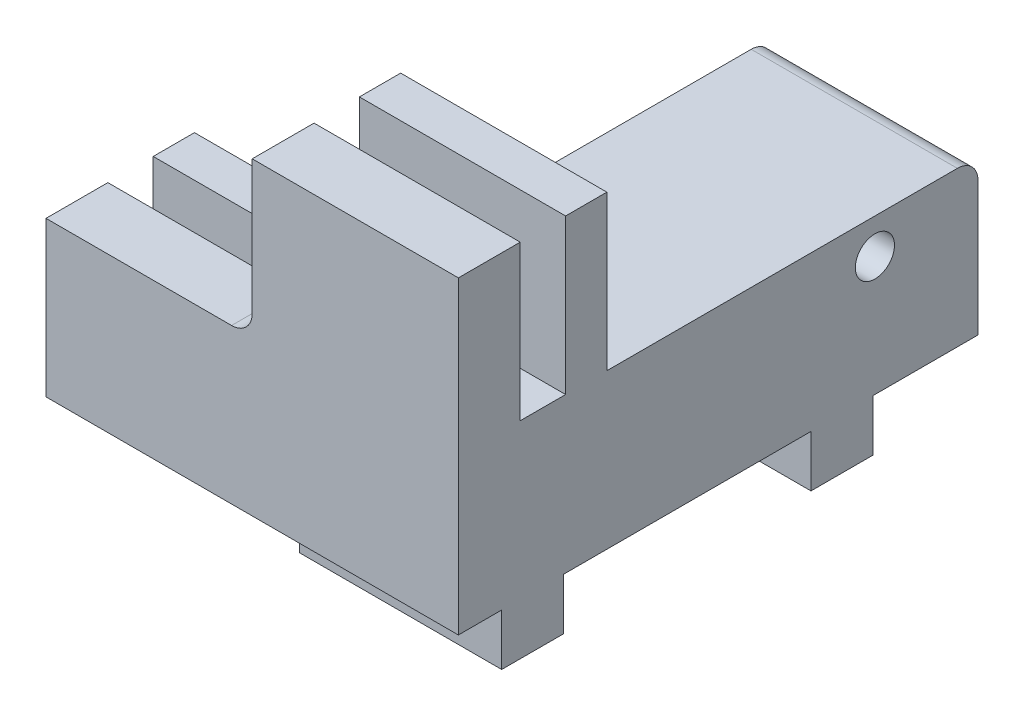
SolidWorks part; units mm, degrees
ref_plane "Front Plane" through (0, 0, 0) normal (0, 0, 1) x (1, 0, 0)
ref_plane "Top Plane" through (0, 0, 0) normal (0, 1, 0) x (1, 0, 0)
ref_plane "Right Plane" through (0, 0, 0) normal (1, 0, 0) x (0, 0, -1)
sketch "Sketch1" plane through (0, 0, 0) normal (1, 0, 0) x (0, 0, -1)
  line L0 (-33.4167, 0) -> (-33.4167, 19.05)
  line L1 (35.2044, 0) -> (-35.2044, 0) construction
  line L2 (-33.4167, 19.05) -> (-25.7967, 19.05)
  line L3 (-25.7967, 19.05) -> (-25.7967, 10.922)
  line L4 (-25.7967, 10.922) -> (-20.2087, 10.922)
  line L5 (-20.2087, 10.922) -> (-20.2087, 19.05)
  line L6 (-20.2087, 19.05) -> (30.5913, 19.05)
  line L7 (30.5913, 19.05) -> (30.5913, 0)
  line L8 (30.5913, 0) -> (-33.4167, 0)
  line L9 (-33.4167, 0) -> (30.5913, 0)
  line L10 (-20.2087, 10.922) -> (17.8913, 10.922)
  line L11 (17.8913, 10.922) -> (17.8913, 14.732)
  line L12 (-15.1287, 19.05) -> (-15.1287, 0)
  circle A0 centre (17.8913, 14.732) radius 2.413
  dimension "D1" = 4.826
  dimension "D2" = 5.588
  dimension "D3" = 8.128
  dimension "D4" = 38.1
  dimension "D5" = 3.81
  dimension "D6" = 50.8
  dimension "D7" = 19.05
  dimension "D8" = 7.62
  dimension "D9" = 5.08
extrude "Boss-Extrude1" add sketch "Sketch1" against normal blind 25.4 contours L12 L10 L4 L3 L2 L0 L9 | L12 L6 L5 L10 region at (0, 7.7154, 25.5352) region at (0, 14.986, 17.6687)
sketch "Sketch2" plane through (0, 0, 0) normal (1, 0, 0) x (0, 0, -1)
  line L0 (-33.4167, 19.05) -> (-33.4167, 38.1)
  line L1 (-33.4167, 38.1) -> (-25.7967, 38.1)
  line L2 (-25.7967, 38.1) -> (-25.7967, 19.05)
  line L3 (-33.4167, 19.05) -> (-33.4167, 0)
  line L4 (-33.4167, 0) -> (-15.1287, 0)
  line L5 (-15.1287, 0) -> (-15.1287, 19.05)
  line L6 (-15.1287, 19.05) -> (-15.1287, 38.1)
  line L7 (-15.1287, 38.1) -> (-20.2087, 38.1)
  line L8 (-20.2087, 38.1) -> (-20.2087, 19.05)
  line L9 (-20.2087, 19.05) -> (-20.2087, 10.922)
  line L10 (-20.2087, 10.922) -> (-25.7967, 10.922)
  line L11 (-25.7967, 10.922) -> (-25.7967, 19.05)
  line L12 (-15.1287, 0) -> (30.5913, 0)
  line L13 (30.5913, 0) -> (30.5913, 19.05)
  line L14 (30.5913, 19.05) -> (-15.1287, 19.05)
  circle A0 centre (17.8913, 14.732) radius 2.413
  line M3 (-15.1287, 0) -> (-15.1287, 19.05)
  line M4 (-15.1287, 19.05) -> (-20.2087, 19.05)
  line M5 (-20.2087, 19.05) -> (-20.2087, 10.922)
  line M6 (-20.2087, 10.922) -> (-25.7967, 10.922)
  line M7 (-25.7967, 10.922) -> (-25.7967, 19.05)
  line M8 (-25.7967, 19.05) -> (-33.4167, 19.05)
  line M9 (-33.4167, 19.05) -> (-33.4167, 0)
  line M10 (-33.4167, 0) -> (-15.1287, 0)
  dimension "D2" = 4.826
  dimension "D1" = 19.05
extrude "Boss-Extrude2" add sketch "Sketch2" along normal blind 0.508 contours M10 M3 M4 M5 M6 M7 M8 M9 | L7 L8 L6 M4 | L2 L1 L0 M8 | L13 L14 L12 A0 M3 region at (0, 8.7063, 24.4631) region at (0, 28.575, 29.6067) region at (0, 9.4133, -7.5133) region at (0, 28.575, 17.6687)
extrude "Boss-Extrude3" add sketch "Sketch2<3>" along normal blind 25.4 contours L13 L14 L12 A0 M3 region at (0, 9.4133, -7.5133)
sketch "Sketch2<3>" plane through (0, 0, 0) normal (1, 0, 0) x (0, 0, -1) same geometry as "Sketch2"
sketch "Sketch3" plane through (0.508, 0, 0) normal (1, 0, 0) x (0, 0, -1)
  line L0 (-33.4167, 38.1) -> (-15.1287, 38.1)
  line L1 (-15.1287, 38.1) -> (-15.1287, 0)
  line L2 (-15.1287, 0) -> (-33.4167, 0)
  line L3 (-33.4167, 0) -> (-33.4167, 38.1)
  line L4 (-25.7967, 38.1) -> (-25.7967, 19.05)
  line L5 (-25.7967, 19.05) -> (-20.2087, 19.05)
  line L6 (-20.2087, 19.05) -> (-20.2087, 38.1)
  line M1 (-15.1287, 0) -> (-15.1287, 19.05)
  line M2 (-15.1287, 19.05) -> (-15.1287, 38.1)
  line M3 (-15.1287, 38.1) -> (-20.2087, 38.1)
  line M4 (-20.2087, 38.1) -> (-20.2087, 10.922)
  line M5 (-20.2087, 10.922) -> (-25.7967, 10.922)
  line M6 (-25.7967, 10.922) -> (-25.7967, 38.1)
  line M7 (-25.7967, 38.1) -> (-33.4167, 38.1)
  line M8 (-33.4167, 38.1) -> (-33.4167, 0)
  line M9 (-33.4167, 0) -> (-15.1287, 0)
extrude "Boss-Extrude6" add sketch "Sketch3" along normal up to surface (24.892 mm away) contours M9 M1 M2 M3 M4 M5 M6 M7 M8 | L5 M6 M5 M4 region at (0.508, 37.6774, 29.6067) region at (0.508, 14.986, 23.0027) up to face at (25.4, 14.732, -20.3043)
fillet "Fillet1" radius 2.54 2 edges at (0, 19.05, 29.6067) (0, 19.05, 17.6687)
fillet "Fillet2" radius 2.54 1 edges at (12.7, 19.05, -30.5913)
sketch "Sketch4" plane through (0, 0, 0) normal (0, -1, 0) x (1, 0, 0)
  line L0 (-25.4, 24.2727) -> (0.508, 24.2727)
  line L1 (-25.4, 15.1287) -> (-25.4, 33.4167) construction
  line L2 (0.508, 24.2727) -> (0.508, 20.4627)
  line L3 (0.508, 20.4627) -> (25.4, 20.4627)
  line L4 (25.4, 33.4167) -> (25.4, -30.5913) construction
  line L5 (0.508, 24.2727) -> (0.508, 28.0827)
  line L6 (0.508, 28.0827) -> (25.4, 28.0827)
  line L7 (25.4, 28.0827) -> (25.4, 20.4627)
  line L8 (25.4, 28.0827) -> (25.4, 20.4627)
  line L9 (25.4, 24.2727) -> (25.4, -13.8273)
  line L10 (25.4, -13.8273) -> (25.4, -10.0173)
  line L11 (25.4, -10.0173) -> (0.508, -10.0173)
  line L12 (0.508, -10.0173) -> (0.508, -17.6373)
  line L13 (0.508, -17.6373) -> (25.4, -17.6373)
  line L14 (25.4, -17.6373) -> (25.4, -13.8273)
  line M11 (25.4, -30.5913) -> (25.4, 33.4167)
  dimension "D1" = 25.908
  dimension "D2" = 3.81
  dimension "D3" = 38.1
  dimension "D4" = 7.62
  dimension "D5" = 3.81
extrude "Boss-Extrude7" add sketch "Sketch4" along normal blind 6.35 contours L6 L5 L2 L3 L8 M11 | L12 L13 L11 M11 region at (12.954, 0, 24.2727) region at (12.954, 0, -13.8273)
